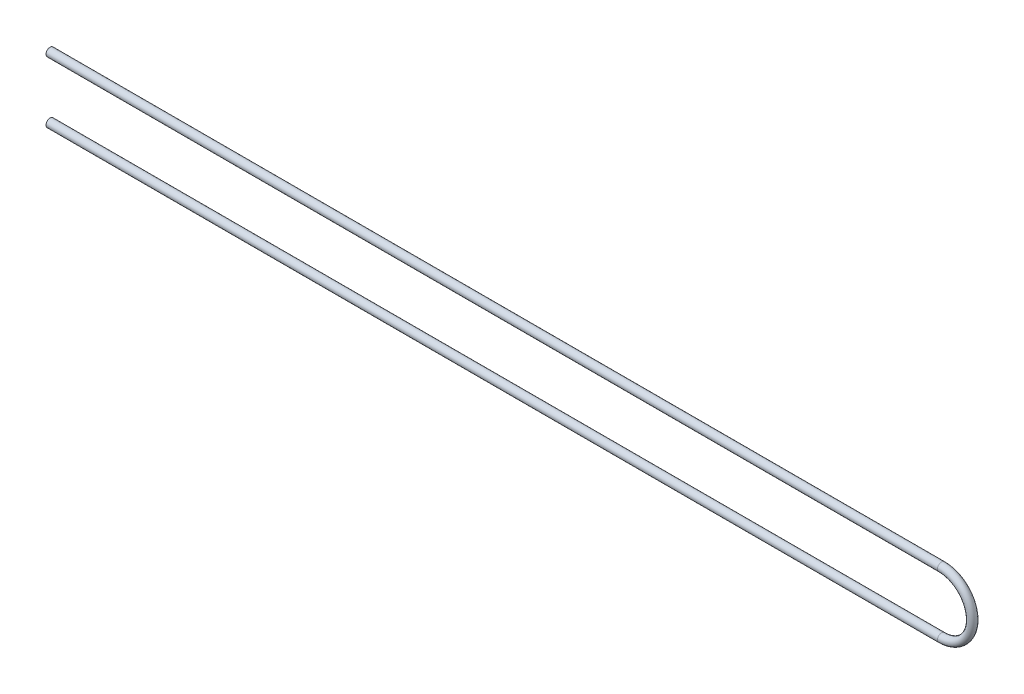
SolidWorks part; units mm, degrees
ref_plane "Front Plane" through (0, 0, 0) normal (0, 0, 1) x (1, 0, 0)
ref_plane "Top Plane" through (0, 0, 0) normal (0, 1, 0) x (1, 0, 0)
ref_plane "Right Plane" through (0, 0, 0) normal (1, 0, 0) x (0, 0, -1)
sketch "Sketch1" plane through (0, 0, 0) normal (0, 0, 1) x (1, 0, 0)
  line L0 (0, 0) -> (2325, 0)
  line L1 (2325, -160) -> (0, -160)
  arc A0 (2325, 0) -> (2325, -160) centre (2325, -80) cw
  dimension "D1" = 2325
  dimension "D2" = 80
sweep "Sweep-Thin1" add path "Sketch1" circular profile diameter 21.3 parameters "D1"=0.5, "D3"=21.3
